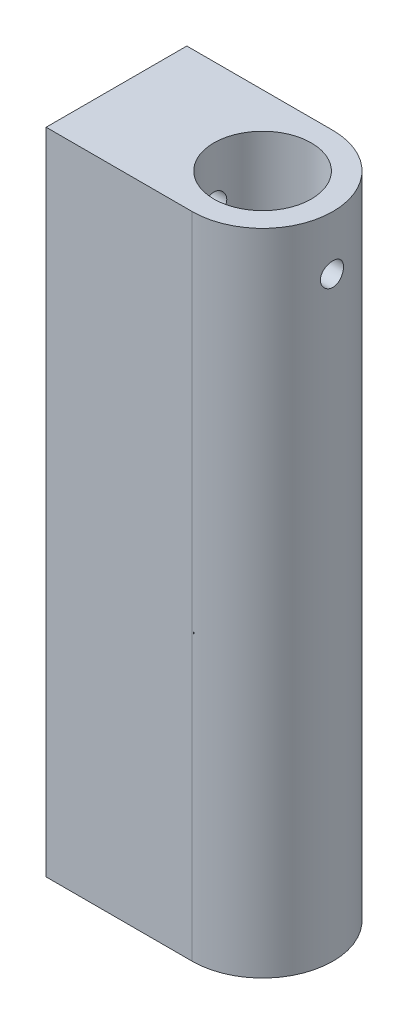
SolidWorks part; units mm, degrees
ref_plane "Front Plane" through (0, 0, 0) normal (0, 0, 1) x (1, 0, 0)
ref_plane "Top Plane" through (0, 0, 0) normal (0, 1, 0) x (1, 0, 0)
ref_plane "Right Plane" through (0, 0, 0) normal (1, 0, 0) x (0, 0, -1)
sketch "Sketch1" plane through (0, 0, 0) normal (0, 1, 0) x (1, 0, 0)
  line L0 (0, 8.255) -> (-17.145, 8.255)
  line L1 (-17.145, 8.255) -> (-17.145, -8.255)
  line L2 (-17.145, -8.255) -> (0, -8.255)
  line L3 (-5.715, 0) -> (-5.715, -8.255) construction
  circle A0 centre (0, 0) radius 5.715
  arc A1 (0, -8.255) -> (0, 8.255) centre (0, 0) ccw
  dimension "D1" = 11.43
  dimension "D2" = 16.51
  dimension "D3" = 11.43
extrude "Boss-Extrude1" add sketch "Sketch1" along normal blind 76.2
sketch "Sketch4" plane through (0, 0, 0) normal (0, -1, 0) x (1, 0, 0)
  circle A0 centre (0, 0) radius 5.715
  circle A1 centre (0, 0) radius 5.08
  circle A2 centre (0, 0) radius 5.715 construction
  dimension "D1" = 10.16
extrude "Boss-Extrude2" add sketch "Sketch4" against normal blind 3.81
hole_wizard "#6-32 Tapped Hole1" positions "Sketch5" profile "Sketch6" tap size "#6-32" standard "ANSI Inch" end condition through all
sketch "Sketch5" plane through (-17.145, 0, 0) normal (-1, 0, 0) x (0, 0, 1)
  line L0 (-8.255, 76.2) -> (8.255, 76.2) construction
  line L1 (8.255, 76.2) -> (8.255, 0) construction
  line L2 (0, 76.2) -> (0, 95.631) construction
  point P0 (0, 69.85)
  dimension "D1" = 6.35
  dimension "D2" = 8.255
sketch "Sketch6" plane through (-17.145, 69.85, 0) normal (0, 1, 0) x (0, 0, 1)
  line L0 (0, 0) -> (0, 25.4)
  line L1 (0, 25.4) -> (1.3525, 25.4)
  line L2 (1.3525, 25.4) -> (1.3525, 0)
  line L5 (1.3525, 0) -> (0, 0)
  line L11 (0, -6.35) -> (0, 107.95) construction
  dimension "Thru Tap Drill Dia." = 2.7051
  dimension "Thru Tap Drill Depth" = 25.4
cosmetic thread "Hole Thread1" parameters "D2"=3.5052
